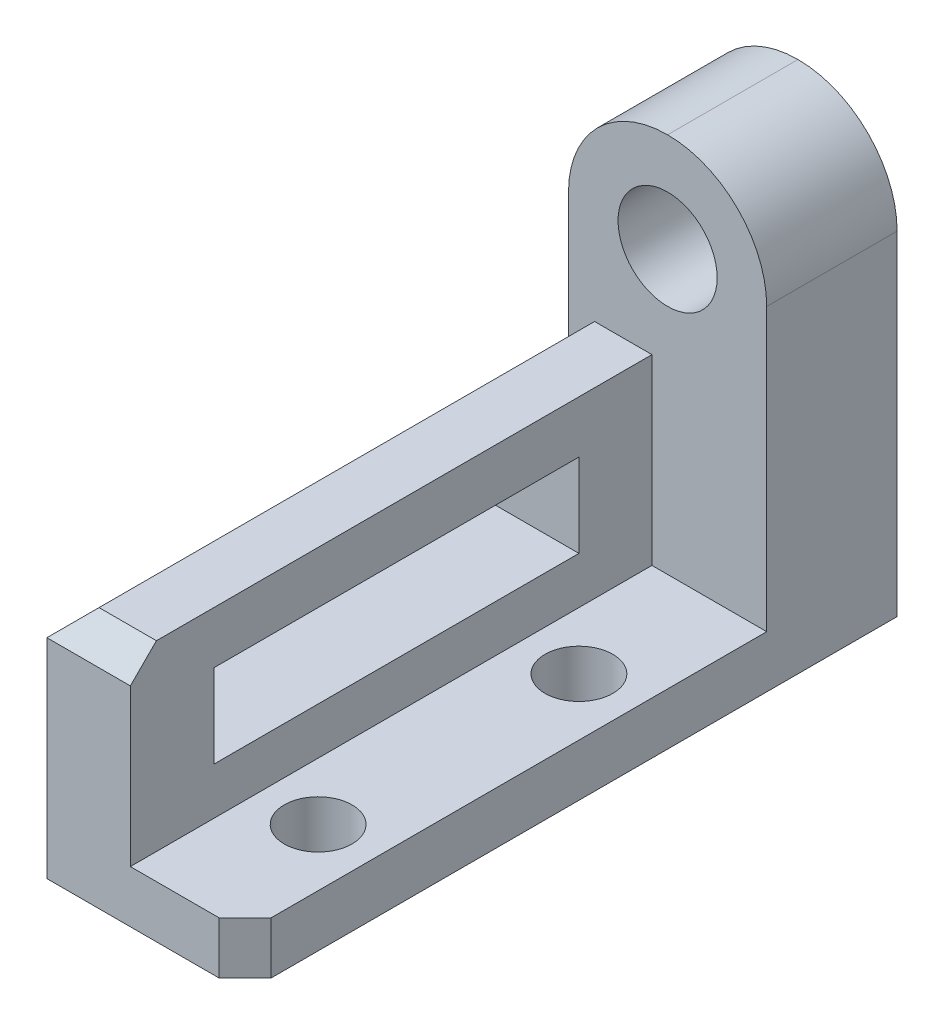
SolidWorks part; units mm, degrees
ref_plane "Front Plane" through (0, 0, 0) normal (0, 0, 1) x (1, 0, 0)
ref_plane "Top Plane" through (0, 0, 0) normal (0, 1, 0) x (1, 0, 0)
ref_plane "Right Plane" through (0, 0, 0) normal (1, 0, 0) x (0, 0, -1)
sketch "Sketch1" plane through (0, 0, 0) normal (1, 0, 0) x (0, 0, -1)
  line L0 (-62.5, 0) -> (62.5, 0)
  line L1 (62.5, 0) -> (62.5, 83)
  line L2 (62.5, 83) -> (37.5, 83)
  line L3 (37.5, 83) -> (37.5, 10)
  line L4 (37.5, 10) -> (-62.5, 10)
  line L5 (-62.5, 10) -> (-62.5, 0)
  line L6 (0, 0) -> (0, 67.9916) construction
  dimension "D1" = 125
  dimension "D2" = 25
  dimension "D3" = 10
  dimension "D4" = 83
extrude "Boss-Extrude1" add sketch "Sketch1" along normal blind 19 and the other way blind 19 contours L0 L1 L2 L3 L4 L5
sketch "Sketch2" plane through (0, 0, -37.5) normal (0, 0, 1) x (1, 0, 0)
  line L0 (-19, 83) -> (-19, 10) construction
  line L1 (-19, 10) -> (19, 10) construction
  line L2 (-19, 45) -> (-19, 10)
  line L3 (-19, 10) -> (-3, 10)
  line L4 (-19, 45) -> (-3, 45)
  line L5 (-3, 45) -> (-3, 10)
  dimension "D1" = 16
  dimension "D2" = 35
extrude "Boss-Extrude2" add sketch "Sketch2" along normal up to surface (100 mm away) up to face at (0, 5, 62.5)
fillet "Fillet1" radius 19 2 edges at (-19, 83, -50) (19, 83, -50)
hole_wizard "Hole1" positions "Sketch3" profile "Sketch5" legacy end condition through all
sketch "Sketch3" plane through (0, 0, -37.5) normal (0, 0, 1) x (1, 0, 0)
  point P0 (0, 64)
sketch "Sketch5" plane through (0, 64, -37.5) normal (1, 0, 0) x (0, -1, 0)
  line L0 (0, 0) -> (0, 25)
  line L1 (0, 25) -> (9.5, 25)
  line L2 (9.5, 25) -> (9.5, 0)
  line L3 (9.5, 0) -> (0, 0)
  line L4 (0, 110) -> (0, -10) construction
  dimension "Diameter" = 19
  dimension "Depth" = 25
chamfer "Chamfer1" distance 5 distance2 5 2 edges at (-19, 45, 12.5) (-11, 45, 62.5)
chamfer "Chamfer2" distance 5 distance2 5 1 edges at (19, 5, 62.5)
sketch "Sketch6" plane through (-3, 0, 0) normal (1, 0, 0) x (0, 0, -1)
  line L0 (-62.5, 10) -> (-62.5, 40) construction
  line L1 (-46.5, 35) -> (23.5, 35)
  line L2 (-46.5, 35) -> (-46.5, 19)
  line L3 (-46.5, 19) -> (23.5, 19)
  line L4 (23.5, 35) -> (23.5, 19)
  line L5 (-57.5, 45) -> (37.5, 45) construction
  dimension "D1" = 16
  dimension "D2" = 16
  dimension "D3" = 70
  dimension "D4" = 10
extrude "Cut-Extrude1" cut sketch "Sketch6" against normal blind 19
hole_wizard "Hole2" positions "Sketch9" profile "Sketch8" legacy end condition through all
sketch "Sketch9" plane through (0, 10, 0) normal (0, 1, 0) x (1, 0, 0)
  line L0 (-3, -62.5) -> (14, -62.5) construction
  line L1 (19, 37.5) -> (19, -57.5) construction
  line L3 (-3, -57.5) -> (-3, 37.5) construction
  point P0 (8, 12.5)
  point P2 (8, -37.5)
  point P7 (0, 0)
  point P8 (5.5823, -37.5)
  point P9 (9.621, -37.5)
  point P10 (8.5069, -37.5)
  dimension "D1" = 50
  dimension "D2" = 25
  dimension "D3" = 22
  dimension "D4" = 11
sketch "Sketch8" plane through (8, 10, -12.5) normal (1, 0, 0) x (0, 0, 1)
  line L0 (0, 0) -> (0, 10)
  line L1 (0, 10) -> (6.5, 10)
  line L2 (6.5, 10) -> (6.5, 0)
  line L3 (6.5, 0) -> (0, 0)
  line L4 (0, 110) -> (0, -10) construction
  dimension "Diameter" = 13
  dimension "Depth" = 10
